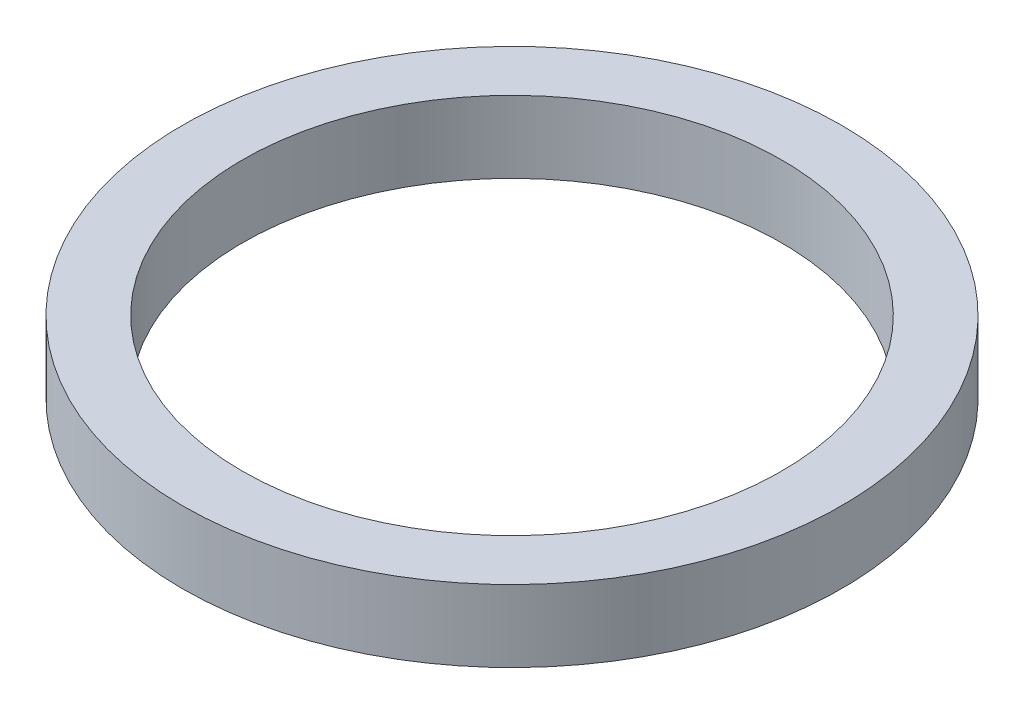
SolidWorks part; units mm, degrees
ref_plane "Front Plane" through (0, 0, 0) normal (0, 0, 1) x (1, 0, 0)
ref_plane "Top Plane" through (0, 0, 0) normal (0, 1, 0) x (1, 0, 0)
ref_plane "Right Plane" through (0, 0, 0) normal (1, 0, 0) x (0, 0, -1)
sketch "Sketch1" plane through (0, 0, 0) normal (0, 1, 0) x (1, 0, 0)
  circle A0 centre (0, 0) radius 55
  dimension "FLANGE_OD" = 110
extrude "Boss-Extrude1" add sketch "Sketch1" along normal blind 12
sketch "Sketch2" plane through (0, 0, 0) normal (0, 1, 0) x (1, 0, 0)
  circle A0 centre (0, 0) radius 45
  dimension "BORE_D" = 90
extrude "Cut-Extrude1" cut sketch "Sketch2" along normal through all
sketch "Sketch3" plane through (0, 12, 0) normal (0, 1, 0) x (1, 0, 0)
  circle A0 centre (0, 0) radius 24.2645 construction
  circle A1 centre (-24.2645, 0) radius 1.7381
  dimension "BOLT_D" = 3.4762
  dimension "BOLT_PCD" = 48.5289
extrude "Cut-Extrude2" cut sketch "Sketch3" against normal blind 8.6401 rebuild error yes
pattern_circular "CirPattern1" count 3 over 360 rebuild error yes
